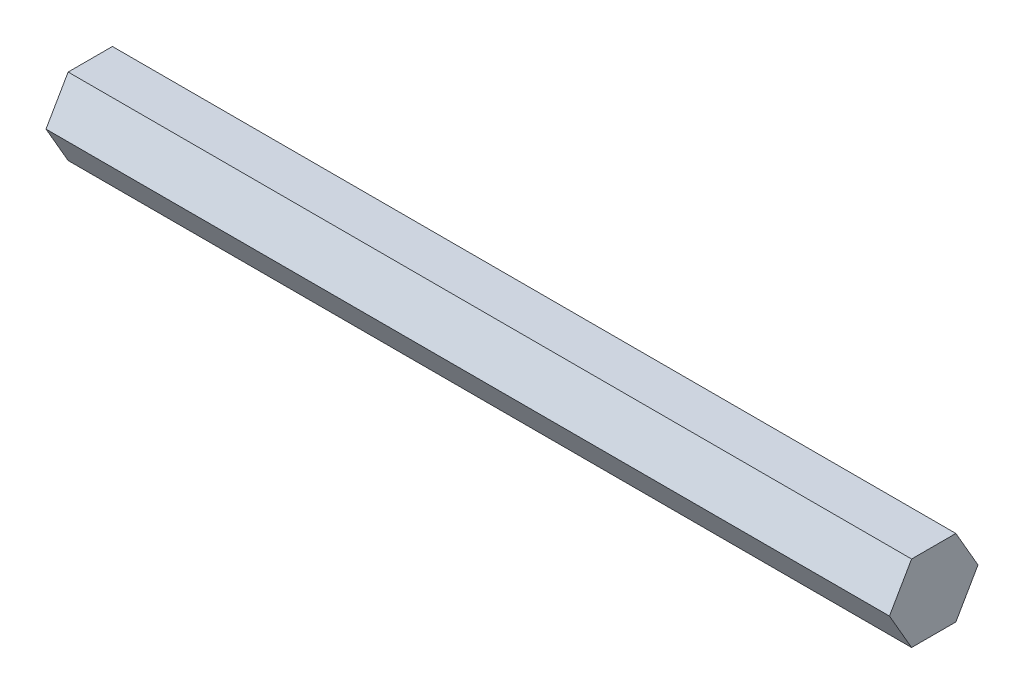
SolidWorks part; units mm, degrees
material "6061-T6 (SS)"
ref_plane "Front" through (0, 0, 0) normal (0, 0, 1) x (1, 0, 0)
ref_plane "Top" through (0, 0, 0) normal (0, 1, 0) x (1, 0, 0)
ref_plane "Right" through (0, 0, 0) normal (1, 0, 0) x (0, 0, -1)
sketch "Sketch1" plane through (0, 0, 0) normal (1, 0, 0) x (0, 0, -1)
  line L1 (7.3323, 0) -> (3.6662, 6.35)
  line L2 (3.6662, 6.35) -> (-3.6662, 6.35)
  line L3 (-3.6662, 6.35) -> (-7.3323, 0)
  line L4 (-7.3323, 0) -> (-3.6662, -6.35)
  line L5 (-3.6662, -6.35) -> (3.6662, -6.35)
  line L6 (3.6662, -6.35) -> (7.3323, 0)
  circle A0 centre (0, 0) radius 6.35 construction
  dimension "D1" = 12.7
extrude "Boss-Extrude1" add sketch "Sketch1" along normal mid plane 139.7
ref_axis "Axis1" through (-80.9, 0, 0) along (1, 0, 0)
